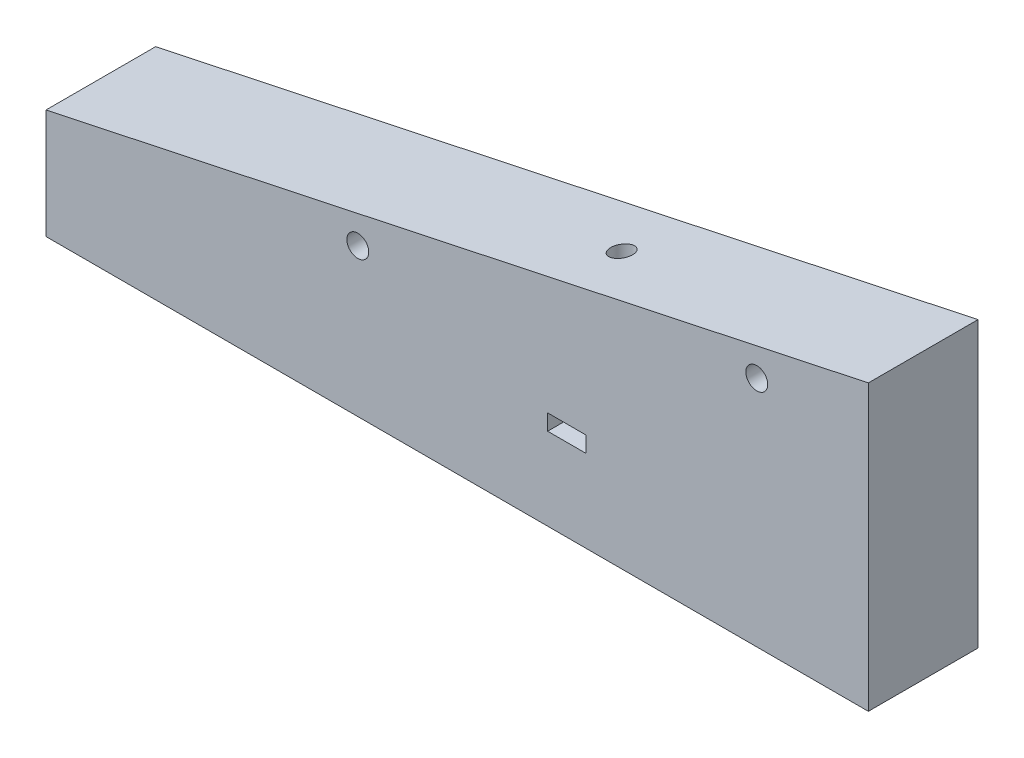
SolidWorks part; units mm, degrees
ref_plane "Front Plane" through (0, 0, 0) normal (0, 0, 1) x (1, 0, 0)
ref_plane "Top Plane" through (0, 0, 0) normal (0, 1, 0) x (1, 0, 0)
ref_plane "Right Plane" through (0, 0, 0) normal (1, 0, 0) x (0, 0, -1)
sketch "Sketch1" plane through (0, 0, 0) normal (0, 1, 0) x (1, 0, 0)
  line L1 (-75, -10) -> (75, -10)
  line L2 (-75, -10) -> (-75, 10)
  line L3 (-75, 10) -> (75, 10)
  line L4 (75, -10) -> (75, 10)
  line L5 (-75, -10) -> (75, 10) construction
  line L6 (-75, 10) -> (75, -10) construction
  point P0 (0, 0)
  dimension "D1" = 20
  dimension "D2" = 150
extrude "Boss-Extrude1" add sketch "Sketch1" along normal mid plane 20
sketch "Sketch2" plane through (0, 0, 0) normal (0, 0, 1) x (1, 0, 0)
  line L0 (-75, 10) -> (75, 10)
  line L1 (75, 10) -> (75, -10) construction
  line L2 (-75, 10) -> (75, 10) construction
  line L3 (75, 10) -> (75, 41.8835)
  line L4 (75, 41.8835) -> (-75, 10)
  dimension "D1" = 12
extrude "Boss-Extrude2" add sketch "Sketch2" along normal mid plane 20
sketch "Sketch3" plane through (0, -10, 0) normal (0, -1, 0) x (1, 0, 0)
  line L0 (28.5359, 0) -> (-28.5359, 0) construction
  line L1 (0, -11) -> (0, 11) construction
  circle A0 centre (20, 0) radius 2
  point P3 (22.4439, -1.3706)
  point P4 (26.2132, 0)
  dimension "D1" = 4
  dimension "D2" = 20
extrude "Cut-Extrude1" cut sketch "Sketch3" against normal through all both
sketch "Sketch4" plane through (0, 0, 10) normal (0, 0, 1) x (1, 0, 0)
  line L1 (16.5, 5) -> (23.5, 5)
  line L2 (16.5, 5) -> (16.5, 7.9)
  line L3 (16.5, 7.9) -> (23.5, 7.9)
  line L4 (23.5, 5) -> (23.5, 7.9)
  line L5 (16.5, 5) -> (23.5, 7.9) construction
  line L6 (16.5, 7.9) -> (23.5, 5) construction
  line L7 (0, -11) -> (0, 11) construction
  line L9 (11, 0) -> (-11, 0) construction
  point P0 (20, 0)
  dimension "D1" = 20
  dimension "D2" = 2.9
  dimension "D3" = 7
  dimension "D4" = 5
extrude "Cut-Extrude2" cut sketch "Sketch4" against normal blind 13.8
sketch "Sketch5" plane through (0, 0, 10) normal (0, 0, 1) x (1, 0, 0)
  line L0 (53.608, 37.3365) -> (54.6476, 32.4457) construction
  line L1 (75, 41.8835) -> (-75, 10) construction
  line L2 (-19.1678, 21.8675) -> (-18.1282, 16.9768) construction
  circle A0 centre (-18.1282, 16.9768) radius 2
  circle A1 centre (54.6476, 32.4457) radius 2
  dimension "D5" = 4
  dimension "D6" = 4
  dimension "D1" = 90
  dimension "D2" = 90
  dimension "D3" = 5
  dimension "D4" = 5
extrude "Cut-Extrude3" cut sketch "Sketch5" against normal through all both and the other way through all
